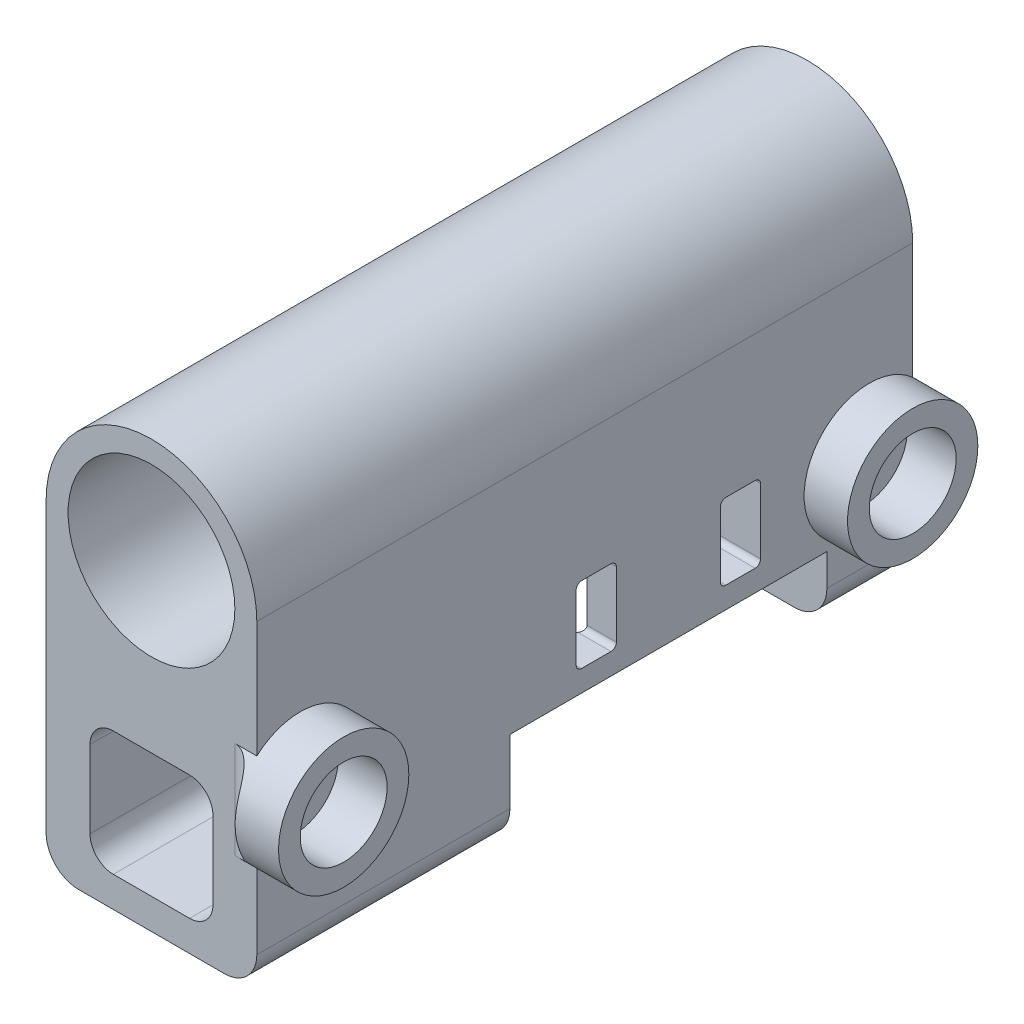
SolidWorks part; units mm, degrees
ref_plane "Front Plane" through (0, 0, 0) normal (0, 0, 1) x (1, 0, 0)
ref_plane "Top Plane" through (0, 0, 0) normal (0, 1, 0) x (1, 0, 0)
ref_plane "Right Plane" through (0, 0, 0) normal (1, 0, 0) x (0, 0, -1)
sketch "Sketch1" plane through (0, 0, 0) normal (0, 0, 1) x (1, 0, 0)
  line L24 (9.7, 0) -> (9.7, -26.58)
  line L54 (-9.7, 0) -> (-9.7, -26.58)
  line L55 (6.7, -29.58) -> (-6.7, -29.58)
  circle A1 centre (0, 0) radius 7.68
  arc A17 (9.7, 0) -> (-9.7, 0) centre (0, 0) ccw
  arc A51 (9.7, -26.58) -> (6.7, -29.58) centre (6.7, -26.58) cw
  arc A52 (-9.7, -26.58) -> (-6.7, -29.58) centre (-6.7, -26.58) ccw
extrude "Boss-Extrude1" add sketch "Sketch1" along normal blind 60.4
sketch "Sketch16" plane through (0, 0, 0) normal (0, 0, -1) x (-1, 0, 0)
  line L0 (-6.7, -29.58) -> (6.7, -29.58)
  line L1 (-9.7, -23.62) -> (-9.7, -26.58)
  line L3 (9.7, -23.62) -> (9.7, -26.58)
  line L5 (-6.7, -26.62) -> (6.7, -26.62)
  arc A0 (-9.7, -26.58) -> (-6.7, -29.58) centre (-6.7, -26.58) ccw
  arc A1 (6.7, -29.58) -> (9.7, -26.58) centre (6.7, -26.58) ccw
  arc A2 (-9.7, -23.62) -> (-6.7, -26.62) centre (-6.7, -23.62) ccw
  arc A3 (6.7, -26.62) -> (9.7, -23.62) centre (6.7, -23.62) ccw
extrude "Cut-Extrude10" cut sketch "Sketch16" against normal offset from surface (30.4 mm away) 30 up to face at (0, -17.3104, 60.4)
sketch "Sketch4" plane through (0, -26.62, 0) normal (0, -1, 0) x (1, 0, 0)
  circle A0 centre (0, 22.5) radius 8.49
extrude "Cut-Extrude2" cut sketch "Sketch4" against normal blind 11 from offset 5.95 offset against normal yes
sketch "Sketch5" plane through (0, -29.58, 0) normal (0, -1, 0) x (1, 0, 0)
  circle A0 centre (0, 22.5) radius 2.5
  circle A1 centre (5.56, 33.0942) radius 1.65
  circle A2 centre (5.56, 11.9058) radius 1.65
  circle A3 centre (-5.56, 11.9058) radius 1.65
  circle A4 centre (-5.56, 33.0942) radius 1.65
extrude "Cut-Extrude3" cut sketch "Sketch5" against normal up to surface (21.9 mm away) up to face at (7.68, 0, 60.4)
sketch "Sketch3" plane through (9.7, 0, 0) normal (1, 0, 0) x (0, 0, -1)
  line L26 (-30.49, -11.7) -> (-27.79, -11.7)
  line L27 (-30.99, -12.2) -> (-30.99, -18.2)
  line L28 (-30.49, -18.7) -> (-27.79, -18.7)
  line L29 (-27.29, -12.2) -> (-27.29, -18.2)
  line L36 (-17.21, -11.7) -> (-14.51, -11.7)
  line L37 (-17.71, -12.2) -> (-17.71, -18.2)
  line L38 (-17.21, -18.7) -> (-14.51, -18.7)
  line L39 (-14.01, -12.2) -> (-14.01, -18.2)
  arc A24 (-14.51, -11.7) -> (-14.01, -12.2) centre (-14.51, -12.2) cw
  arc A25 (-14.51, -18.7) -> (-14.01, -18.2) centre (-14.51, -18.2) ccw
  arc A26 (-17.71, -18.2) -> (-17.21, -18.7) centre (-17.21, -18.2) ccw
  arc A27 (-17.21, -11.7) -> (-17.71, -12.2) centre (-17.21, -12.2) ccw
  arc A28 (-27.79, -11.7) -> (-27.29, -12.2) centre (-27.79, -12.2) cw
  arc A29 (-27.79, -18.7) -> (-27.29, -18.2) centre (-27.79, -18.2) ccw
  arc A30 (-30.99, -18.2) -> (-30.49, -18.7) centre (-30.49, -18.2) ccw
  arc A31 (-30.49, -11.7) -> (-30.99, -12.2) centre (-30.49, -12.2) ccw
  circle A32 centre (-4, -15.2) radius 1.65
  circle A33 centre (-56.4, -15.2) radius 1.65
extrude "Cut-Extrude1" cut sketch "Sketch3" against normal up to next
sketch "Sketch6" plane through (0, -29.58, 0) normal (0, -1, 0) x (1, 0, 0)
  line L42 (-9.7, 37.0942) -> (9.7, 37.0942)
  line L43 (-9.7, 37.0942) -> (-9.7, 7.9058)
  line L44 (-9.7, 7.9058) -> (9.7, 7.9058)
  line L45 (9.7, 37.0942) -> (9.7, 7.9058)
extrude "Cut-Extrude4" cut sketch "Sketch6" against normal up to surface (8.91 mm away) up to face at (0, -20.67, 20)
sketch "Sketch7" plane through (0, -9.67, 0) normal (0, -1, 0) x (1, 0, 0)
  circle A0 centre (0, 22.5) radius 2.5
  circle A1 centre (0, 22.5) radius 3.5
extrude "Boss-Extrude2" add sketch "Sketch7" along normal blind 0.4
sketch "Sketch8" plane through (0, 0, 0) normal (0, 0, -1) x (-1, 0, 0)
  line L0 (3.5, -18) -> (3.5, -18.7)
  line L1 (3, -17.5) -> (-3, -17.5)
  line L2 (-3.5, -18) -> (-3.5, -18.7)
  line L3 (3, -19.2) -> (-3, -19.2)
  arc A0 (-3, -19.2) -> (-3.5, -18.7) centre (-3, -18.7) cw
  arc A1 (-3, -17.5) -> (-3.5, -18) centre (-3, -18) ccw
  arc A2 (3.5, -18.7) -> (3, -19.2) centre (3, -18.7) cw
  arc A3 (3, -17.5) -> (3.5, -18) centre (3, -18) cw
extrude "Cut-Extrude5" cut sketch "Sketch8" against normal up to next
sketch "Sketch9" plane through (0, 0, 60.4) normal (0, 0, 1) x (1, 0, 0)
  line L12 (3.51, -26.77) -> (-3.51, -26.77)
  line L17 (5.66, -24.62) -> (5.66, -17.49)
  line L18 (3.51, -15.34) -> (-3.51, -15.34)
  line L19 (-5.66, -24.62) -> (-5.66, -17.49)
  arc A13 (-3.51, -15.34) -> (-5.66, -17.49) centre (-3.51, -17.49) ccw
  arc A14 (5.66, -17.49) -> (3.51, -15.34) centre (3.51, -17.49) ccw
  arc A15 (-3.51, -26.77) -> (-5.66, -24.62) centre (-3.51, -24.62) cw
  arc A16 (3.51, -26.77) -> (5.66, -24.62) centre (3.51, -24.62) ccw
sketch "Sketch11" plane through (0, 0, 60.4) normal (0, 0, 1) x (1, 0, 0)
  circle A1 centre (0, -22.91) radius 1.7
extrude "Cut-Extrude8" cut sketch "Sketch9" against normal up to surface (23.3058 mm away) up to face at (0, -25.8171, 37.0942)
sketch "Sketch14" plane through (-9.7, 0, 0) normal (-1, 0, 0) x (0, 0, 1)
  circle A0 centre (4, -15.2) radius 3.3
  circle A1 centre (56.4, -15.2) radius 3.3
extrude "Cut-Extrude9" cut sketch "Sketch14" against normal blind 2
extrude "Cut-Extrude11" cut sketch "Sketch11" against normal up to surface (60.4 mm away) up to face at (0, -18.35, 0)
sketch "Sketch17" plane through (9.7, 0, 0) normal (1, 0, 0) x (0, 0, -1)
  circle A0 centre (-56.4, -15.2) radius 1.65
  circle A1 centre (-4, -15.2) radius 1.65
  circle A2 centre (-4, -15.2) radius 6
  circle A3 centre (-56.4, -15.2) radius 6
extrude "Boss-Extrude3" add sketch "Sketch17" along normal blind 4
fillet "Fillet1" radius 2 2 edges at (9.7, -15.2, 60.4) (9.7, -15.2, 0)
sketch "Sketch18" plane through (13.7, 0, 0) normal (1, 0, 0) x (0, 0, -1)
  circle A0 centre (-56.4, -15.2) radius 4
  circle A1 centre (-4, -15.2) radius 4
extrude "Cut-Extrude12" cut sketch "Sketch18" against normal blind 4.5
sketch "Sketch24" plane through (0, -20.67, 0) normal (0, -1, 0) x (1, 0, 0)
  line L1 (5.56, 29.7456) -> (8.46, 31.4199)
  line L2 (8.46, 31.4199) -> (8.46, 34.7685)
  line L3 (8.46, 34.7685) -> (5.56, 36.4429)
  line L4 (5.56, 36.4429) -> (2.66, 34.7685)
  line L5 (2.66, 34.7685) -> (2.66, 31.4199)
  line L6 (2.66, 31.4199) -> (5.56, 29.7456)
  line L7 (-5.56, 29.7456) -> (-2.66, 31.4199)
  line L8 (-2.66, 31.4199) -> (-2.66, 34.7685)
  line L9 (-2.66, 34.7685) -> (-5.56, 36.4429)
  line L10 (-5.56, 36.4429) -> (-8.46, 34.7685)
  line L11 (-8.46, 34.7685) -> (-8.46, 31.4199)
  line L12 (-8.46, 31.4199) -> (-5.56, 29.7456)
  line L13 (-5.56, 8.5571) -> (-2.66, 10.2315)
  line L14 (-2.66, 10.2315) -> (-2.66, 13.5801)
  line L15 (-2.66, 13.5801) -> (-5.56, 15.2544)
  line L16 (-5.56, 15.2544) -> (-8.46, 13.5801)
  line L17 (-8.46, 13.5801) -> (-8.46, 10.2315)
  line L18 (-8.46, 10.2315) -> (-5.56, 8.5571)
  line L19 (5.56, 8.5571) -> (8.46, 10.2315)
  line L20 (8.46, 10.2315) -> (8.46, 13.5801)
  line L21 (8.46, 13.5801) -> (5.56, 15.2544)
  line L22 (5.56, 15.2544) -> (2.66, 13.5801)
  line L23 (2.66, 13.5801) -> (2.66, 10.2315)
  line L24 (2.66, 10.2315) -> (5.56, 8.5571)
  circle A0 centre (5.56, 33.0942) radius 2.9 construction
  circle A1 centre (-5.56, 33.0942) radius 2.9 construction
  circle A2 centre (-5.56, 11.9058) radius 2.9 construction
  circle A3 centre (5.56, 11.9058) radius 2.9 construction
extrude "Cut-Extrude13" cut sketch "Sketch24" against normal blind 7 from offset 11 offset against normal yes
